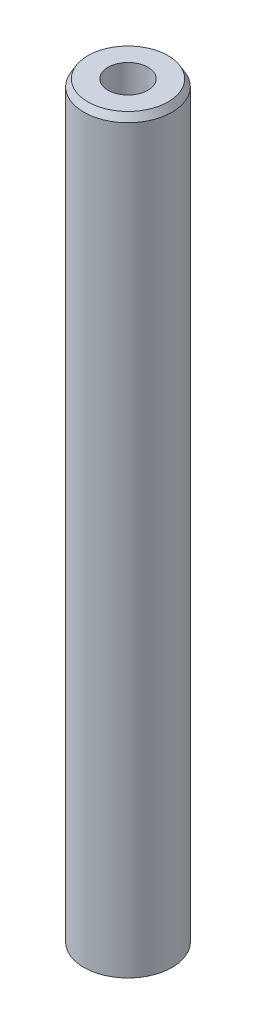
SolidWorks part; units mm, degrees
ref_plane "Front Plane" through (0, 0, 0) normal (0, 0, 1) x (1, 0, 0)
ref_plane "Top Plane" through (0, 0, 0) normal (0, 1, 0) x (1, 0, 0)
ref_plane "Right Plane" through (0, 0, 0) normal (1, 0, 0) x (0, 0, -1)
sketch "Sketch1" plane through (0, 0, 0) normal (0, 1, 0) x (1, 0, 0)
  circle A0 centre (0, 0) radius 35
  dimension "SHAFT_OD" = 70
extrude "Boss-Extrude1" add sketch "Sketch1" along normal blind 596.4068
sketch "Sketch2" plane through (0, 0, 0) normal (0, 1, 0) x (1, 0, 0)
  circle A0 centre (0, 0) radius 15.8222
  dimension "BORE_D" = 31.6444
extrude "Cut-Extrude1" cut sketch "Sketch2" along normal through all
chamfer "Chamfer1" distance 5.4918 angle 30 2 edges at (0, 596.4068, 35) (0, 0, 35) first distance on face at (0, 596.4068, 35) first distance on face at (0, 0, 15.8222)
